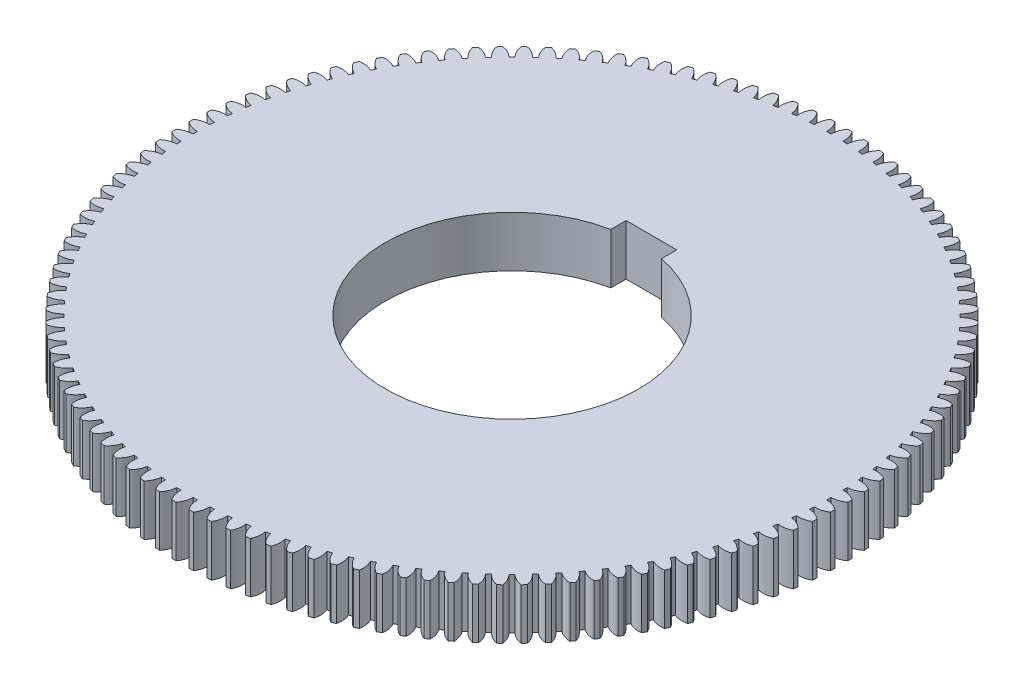
SolidWorks part; units mm, degrees
ref_plane "Ön Düzlem" through (0, 0, 0) normal (0, 0, 1) x (1, 0, 0)
ref_plane "Üst Düzlem" through (0, 0, 0) normal (0, 1, 0) x (1, 0, 0)
ref_plane "Sağ Düzlem" through (0, 0, 0) normal (1, 0, 0) x (0, 0, -1)
sketch "Çizim1" plane through (0, 0, 0) normal (0, 1, 0) x (1, 0, 0)
  circle A0 centre (0, 0) radius 13
  dimension "D1" = 26
extrude "Yükseklik-Ekstrüzyon1" add sketch "Çizim1" along normal blind 2
sketch "Çizim2" plane through (0, 2, 0) normal (0, 1, 0) x (1, 0, 0)
  line L0 (0, 0) -> (0, 13) construction
  line L1 (-0.0875, 12.5) -> (0.0875, 12.5)
  circle A0 centre (0, 0) radius 13 construction
  arc A1 (-0.0875, 12.5) -> (-0.35, 13.1) centre (-0.8875, 12.5074) ccw
  arc A2 (0.0875, 12.5) -> (0.35, 13.1) centre (0.8875, 12.5074) cw
  arc A3 (-0.35, 13.1) -> (0.35, 13.1) centre (0, 12.6173) cw
  point P11 (0, 12.5)
  dimension "D4" = 0.8
  dimension "D5" = 12.5
  dimension "D1" = 0.175
  dimension "D2" = 0.7
  dimension "D3" = 0.6
extrude "Kes-Ekstrüzyon1" cut sketch "Çizim2" against normal through all
sketch "Çizim3" plane through (0, 2, 0) normal (0, 1, 0) x (1, 0, 0)
  line L1 (-1, 0) -> (1, 0)
  line L2 (-1, 0) -> (-1, 5.5)
  line L3 (-1, 5.5) -> (1, 5.5)
  line L4 (1, 0) -> (1, 5.5)
  circle A0 centre (0, 0) radius 7.5
  circle A1 centre (0, 0) radius 5
  dimension "D1" = 10
  dimension "D2" = 15
  dimension "D3" = 5.5
  dimension "D4" = 2
extrude "Kes-Ekstrüzyon2" cut sketch "Çizim3" against normal through all contours L4 A1 L2 L1 | L2 A1 L4 L1 | L2 L1 L4 L3 region at (0, 2, -2.4833) region at (0, 2, 0.3595)
pattern_circular "Dairesel Kaplama1" count 120 over 360 about axis through (0, 0, 0) along (0, 1, 0) of "Kes-Ekstrüzyon1" reverse direction yes
